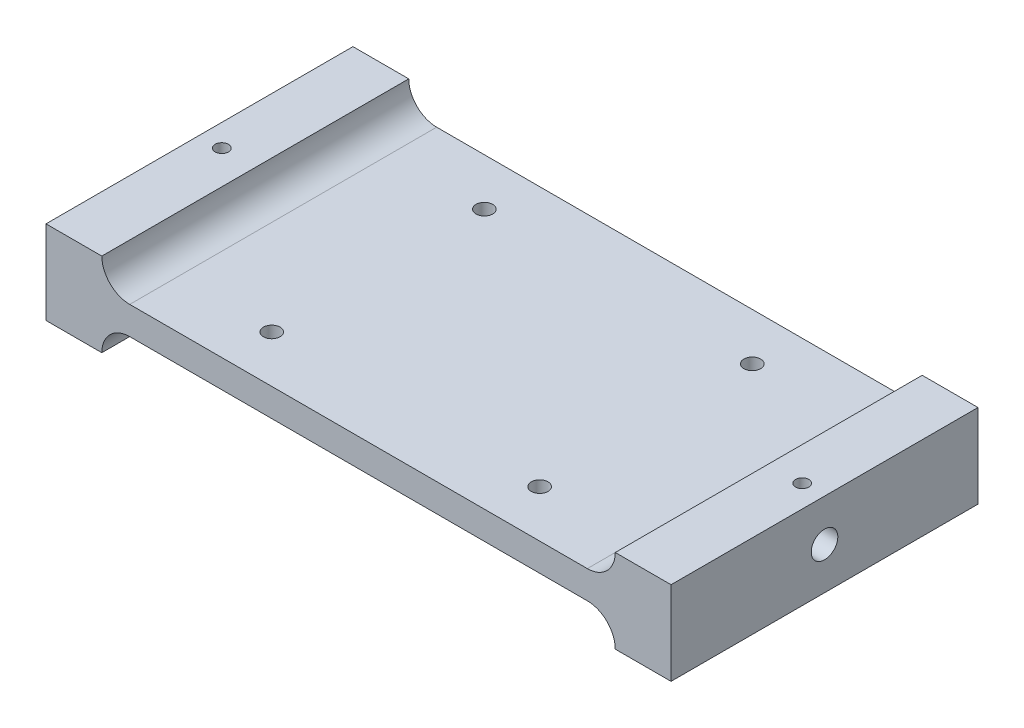
SolidWorks part; units mm, degrees
ref_plane "Front Plane" through (0, 0, 0) normal (0, 0, 1) x (1, 0, 0)
ref_plane "Top Plane" through (0, 0, 0) normal (0, 1, 0) x (1, 0, 0)
ref_plane "Right Plane" through (0, 0, 0) normal (1, 0, 0) x (0, 0, -1)
sketch "Sketch1" plane through (0, 0, 0) normal (0, 1, 0) x (1, 0, 0)
  line L0 (-24, 0) -> (24, 0) construction
  line L1 (-24, 19.05) -> (24, 19.05)
  line L2 (-24, 19.05) -> (-24, -19.05)
  line L3 (-24, -19.05) -> (24, -19.05)
  line L4 (24, 19.05) -> (24, -19.05)
  line L5 (-24, 19.05) -> (24, -19.05) construction
  line L6 (-24, -19.05) -> (24, 19.05) construction
  line L8 (-46, 27.5) -> (46, 27.5)
  line L9 (-46, 27.5) -> (-46, -27.5)
  line L10 (-46, -27.5) -> (46, -27.5)
  line L11 (46, 27.5) -> (46, -27.5)
  line L12 (-46, 27.5) -> (46, -27.5) construction
  line L13 (-46, -27.5) -> (46, 27.5) construction
  circle A0 centre (-24, 19.05) radius 1.5
  circle A1 centre (24, 19.05) radius 1.5
  circle A2 centre (-24, -19.05) radius 1.5
  circle A3 centre (24, -19.05) radius 1.5
  point P0 (0, 0)
  point P12 (0, 0)
  dimension "D3" = 3
  dimension "D4" = 3
  dimension "D5" = 3
  dimension "D6" = 3
  dimension "D1" = 38.1
  dimension "D2" = 48
  dimension "D7" = 55
  dimension "D8" = 92
extrude "Boss-Extrude3" add sketch "Sketch1" along normal mid plane 5 contours A3 L4 A1 L1 A0 L2 A2 L3 | L11 L8 L9 L10 A3 L3 A2 L2 A0 L1 A1 L4 region at (0, 0, 0) region at (0, 0, -26.4281)
sketch "Sketch4" plane through (46, 0, 0) normal (1, 0, 0) x (0, 0, -1)
  line L0 (27.5, 2.5) -> (27.5, -2.5) construction
  line L1 (-27.5, 7.5) -> (27.5, 7.5)
  line L2 (-27.5, 7.5) -> (-27.5, -7.5)
  line L3 (-27.5, -7.5) -> (27.5, -7.5)
  line L4 (27.5, 7.5) -> (27.5, -7.5)
  line L5 (-27.5, 7.5) -> (27.5, -7.5) construction
  line L6 (-27.5, -7.5) -> (27.5, 7.5) construction
  point P1 (0, 0)
  dimension "D1" = 15
extrude "Boss-Extrude4" add sketch "Sketch4" along normal blind 10
sketch "Sketch5" plane through (-46, 0, 0) normal (-1, 0, 0) x (0, 0, 1)
  line L1 (-27.5, 7.5) -> (27.5, 7.5)
  line L2 (-27.5, 7.5) -> (-27.5, -7.5)
  line L3 (-27.5, -7.5) -> (27.5, -7.5)
  line L4 (27.5, 7.5) -> (27.5, -7.5)
  line L5 (-27.5, 7.5) -> (27.5, -7.5) construction
  line L6 (-27.5, -7.5) -> (27.5, 7.5) construction
  point P0 (0, 0)
extrude "Boss-Extrude5" add sketch "Sketch5" along normal blind 10
sketch "Sketch6" plane through (56, 0, 0) normal (1, 0, 0) x (0, 0, -1)
  circle A0 centre (0, 0) radius 2.3813
  dimension "D1" = 4.7625
extrude "Cut-Extrude1" cut sketch "Sketch6" against normal blind 8
sketch "Sketch7" plane through (0, 7.5, 0) normal (0, 1, 0) x (1, 0, 0)
  line L0 (56, 0) -> (46, 0) construction
  line L1 (56, 27.5) -> (56, -27.5) construction
  line L2 (46, 27.5) -> (46, -27.5) construction
  line L3 (0, 27.5) -> (0, -27.5) construction
  line L4 (-46, 27.5) -> (46, 27.5) construction
  line L5 (-46, -27.5) -> (46, -27.5) construction
  circle A0 centre (52, 0) radius 1.1906
  circle A1 centre (-52, 0) radius 1.1906
  dimension "D2" = 2.3813
  dimension "D1" = 4
extrude "Cut-Extrude2" cut sketch "Sketch7" against normal up to next
sketch "Sketch8" plane through (-56, 0, 0) normal (-1, 0, 0) x (0, 0, 1)
  circle A0 centre (0, 0) radius 2.3813
  dimension "D1" = 4.7625
extrude "Cut-Extrude4" cut sketch "Sketch8" against normal blind 8
fillet "Fillet1" radius 5 4 edges at (-46, -2.5, 0) (46, -2.5, 0) (46, 2.5, 0) (-46, 2.5, 0)
